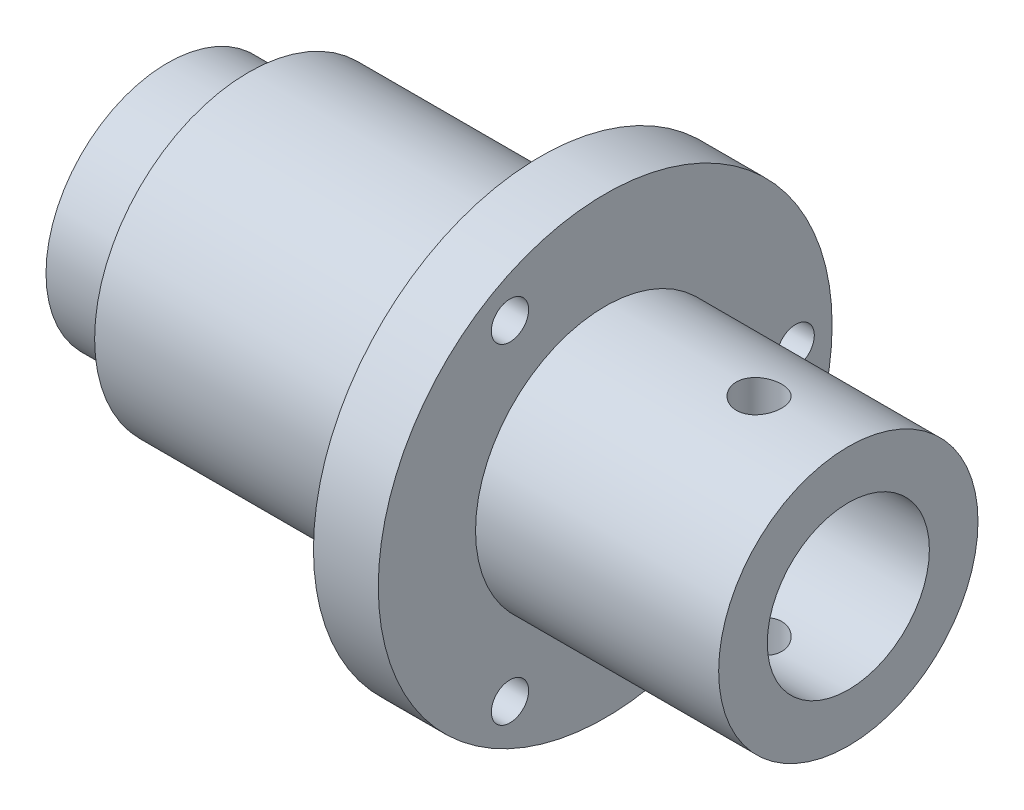
SolidWorks part; units mm, degrees
ref_plane "Front Plane" through (0, 0, 0) normal (0, 0, 1) x (1, 0, 0)
ref_plane "Top Plane" through (0, 0, 0) normal (0, 1, 0) x (1, 0, 0)
ref_plane "Right Plane" through (0, 0, 0) normal (1, 0, 0) x (0, 0, -1)
sketch "Sketch1" plane through (0, 0, 0) normal (0, 1, 0) x (1, 0, 0)
  line L0 (0, 0) -> (23.1328, 0) construction
  line L1 (0, 5) -> (27, 5)
  line L2 (0, 5) -> (0, 7.5)
  line L3 (0, 7.5) -> (5, 7.5)
  line L4 (5, 7.5) -> (5, 9.5)
  line L5 (5, 9.5) -> (23, 9.5)
  line L6 (23, 9.5) -> (23, 14)
  line L7 (23, 14) -> (27, 14)
  line L8 (27, 14) -> (27, 5)
  dimension "D1" = 10
  dimension "D2" = 19
  dimension "D3" = 2.5
  dimension "D4" = 5
  dimension "D5" = 18
  dimension "D6" = 28
  dimension "D7" = 4
revolve "Revolve1" add sketch "Sketch1" angle 360 about L0
sketch "Sketch2" plane through (23, 0, 0) normal (-1, 0, 0) x (0, 0, 1)
  line L1 (-9.5, 0) -> (-14, 0) construction
  circle A0 centre (0, 0) radius 9.5 construction
  circle A1 centre (0, 0) radius 14 construction
  circle A2 centre (-11.75, 0) radius 1.15
  dimension "D1" = 2.3
extrude "Cut-Extrude1" cut sketch "Sketch2" against normal through all
pattern_circular "CirPattern1" count 3 over 360 about axis through (0, 0, 0) along (-1, 0, 0) of "Cut-Extrude1"
sketch "Sketch3" plane through (27, 0, 0) normal (1, 0, 0) x (0, 0, -1)
  circle A0 centre (0, 0) radius 5
  circle A1 centre (0, 0) radius 8
  circle A2 centre (0, 0) radius 5 construction
  dimension "D1" = 3
extrude "Boss-Extrude1" add sketch "Sketch3" along normal blind 15
sketch "Sketch4" plane through (0, 0, 0) normal (0, 1, 0) x (1, 0, 0)
  circle A0 centre (36.4944, 0) radius 1.4
  dimension "D1" = 2.8
extrude "Cut-Extrude2" cut sketch "Sketch4" against normal mid plane 30
